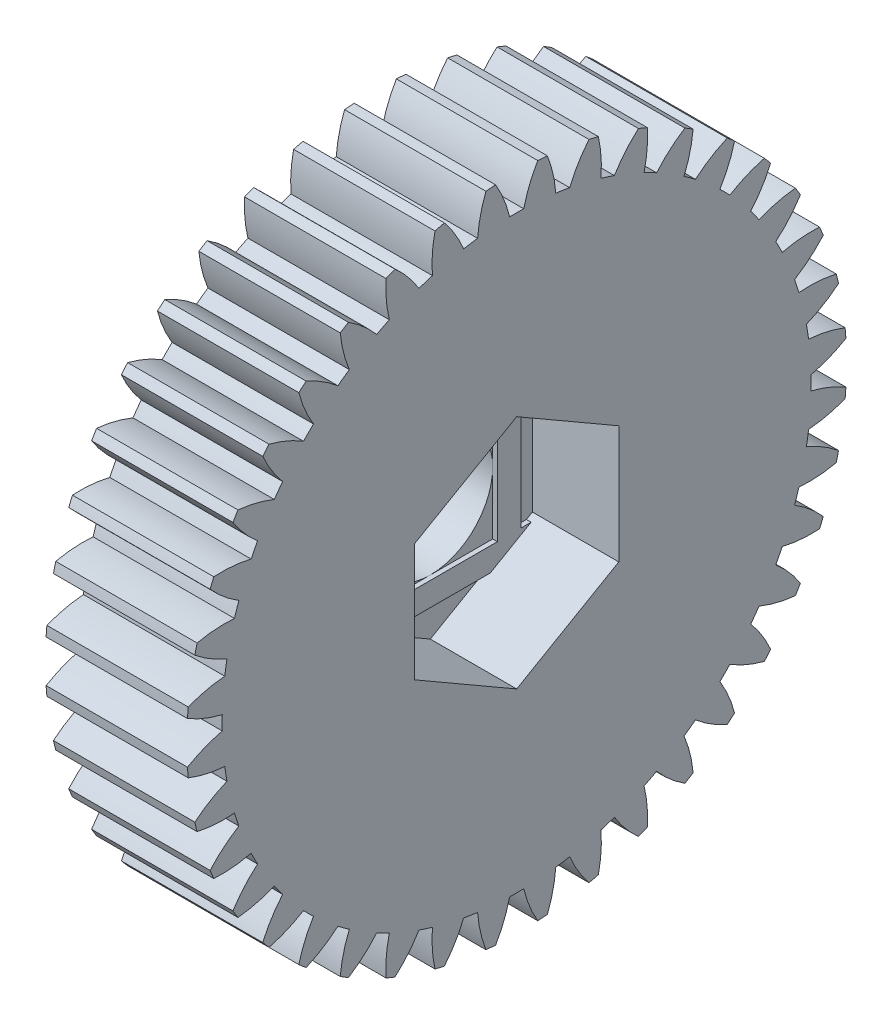
SolidWorks part; units mm, degrees
ref_plane "Plane1" through (0, 0, 0) normal (0, 0, 1) x (1, 0, 0)
ref_plane "Plane2" through (0, 0, 0) normal (0, 1, 0) x (1, 0, 0)
ref_plane "Plane3" through (0, 0, 0) normal (1, 0, 0) x (0, 0, -1)
sketch "HoldingSke" plane through (0, 0, 0) normal (0, 1, 0) x (1, 0, 0)
  line L0 (0, 0) -> (0.766, -0.6428)
  line L1 (-15, 0) -> (100, 0) construction
  line L2 (0, 0) -> (-2.1039, 2.3779)
  line L3 (0, 0) -> (-11.863, 4.5341)
  line L4 (0, 0) -> (6.6156, 5.5511)
  line L5 (0, 0) -> (-46.8476, -17.4728)
  line L6 (0, 0) -> (-7.4607, -5.0337)
  line L7 (-2.1039, 2.3779) -> (8.6586, 51.2059)
  line L8 (-76.2, 54.61) -> (-75.5, 54.61)
  line L9 (-71.009, 38.7566) -> (-53.1078, 45.2721)
  line L10 (-76.2, 71.12) -> (104.1128, 71.12)
  line L11 (0, 0) -> (-9, 0)
  line L12 (-76.2, 101.6) -> (-76.162, 101.6)
  line L13 (24.9733, 27.94) -> (52.9518, 28.4284)
  line L14 (24.9733, 27.94) -> (24.9743, 27.94)
  line L15 (24.9733, 27.94) -> (100.4006, 29.5858)
  line L16 (-63.627, -1) -> (-12.827, -1)
  circle A0 centre (0, 0) radius 2
  circle A1 centre (0, 0) radius 18.749
  circle A2 centre (0, 0) radius 37.5
  circle A3 centre (0, 0) radius 2
  dimension "MHD" = 37.498
  dimension "Hub_dia" = 75
  dimension "Bore" = 4
  dimension "MBD" = 4
  dimension "Num_teeth" = 40
  dimension "Pitch" = 1
  dimension "Overall_len" = 50
  dimension "Show_teeth" = 40
  dimension "Thickness" = 9
  dimension "OAL" = 50.0001
  dimension "T_dim" = 0.7
  dimension "Ap" = 20
  dimension "H" = 19.05
  dimension "Pitch_radius" = 180.3128
  dimension "Width" = 9
  dimension "Backlash" = 0.038
  dimension "Addendum_fac" = 1
  dimension "Dedendum_fac" = 1.25
  dimension "Clearance_fac" = 0.25
  dimension "Dedendum_add" = 0.001
  dimension "Module" = 1
sketch "BasProSke" plane through (0, 0, 0) normal (0, 1, 0) x (1, 0, 0)
  line L0 (-10, 0) -> (60, 0) construction
  line L1 (0, 0) -> (0, 21)
  line L2 (0, 0) -> (9, 0)
  line L3 (9, 0) -> (9, 21)
  line L4 (9, 21) -> (0, 21)
  dimension "Thickness" = 9
  dimension "Diameter" = 42
revolve "Base-Revolve" add sketch "BasProSke" angle 360 about L0
sketch "TooCutSke" plane through (0, 0, 0) normal (1, 0, 0) x (0, 0, -1)
  line L1 (0, 0) -> (0, 107) construction
  line L2 (0, 0) -> (-0.8517, 19.9819) construction
  line L3 (0, 0) -> (-3.1363, 39.8509) construction
  line L4 (-0.8517, 19.9819) -> (-1.5682, 19.9255) construction
  arc A0 (0.4487, 18.7436) -> (-0.4487, 18.7436) centre (0, 0) ccw
  arc A1 (1.3547, 20.9817) -> (-1.3547, 20.9817) centre (0, 0) ccw
  circle A2 centre (0, 0) radius 20 construction
  circle A3 centre (0, 0) radius 18.7939 construction
  arc A4 (-0.4487, 18.7436) -> (-1.3547, 20.9817) centre (-8.2322, 16.895) ccw
  arc A5 (1.3547, 20.9817) -> (0.4487, 18.7436) centre (8.2322, 16.895) ccw
  dimension "Root_dia" = 37.498
  dimension "Overcut_dia" = 42.0508
  dimension "Pitch_dia" = 40
  dimension "Base_dia" = 37.5877
  dimension "Flank_rad" = 8
  dimension "Half_ang" = 4.5
  dimension "Half_CT" = 0.7187
extrude "ToothCut" cut sketch "TooCutSke" along normal through all
fillet "Breaks" [suppressed] radius 0.02 tangent propagation no
fillet "RootFillets" [suppressed] radius 0.251
pattern_circular "TeethCuts" count 40 every 9 about axis through (-10, 0, 0) along (1, 0, 0) of "ToothCut", "RootFillets", "Breaks"
sketch "HubNeaOneSke" plane through (0, 0, 0) normal (-1, 0, 0) x (0, 0, 1)
  circle A0 centre (0, 0) radius 18.749
  dimension "Diameter" = 37.498
extrude "HubNearOne" [suppressed] add sketch "HubNeaOneSke" along normal blind 41.0001
sketch "HubNeaBotSke" plane through (0, 0, 0) normal (-1, 0, 0) x (0, 0, 1)
  circle A0 centre (0, 0) radius 18.749
  dimension "Diameter" = 37.498
extrude "HubNearBoth" [suppressed] add sketch "HubNeaBotSke" along normal blind 20.5
ref_plane "FarPln" through (9, 0, 0) normal (1, 0, 0) x (0, 0, -1)
sketch "HubFarSke" plane through (9, 0, 0) normal (1, 0, 0) x (0, 0, -1)
  circle A0 centre (0, 0) radius 18.749
  dimension "Diameter" = 37.498
extrude "HubFar" [suppressed] add sketch "HubFarSke" along normal blind 20.5
sketch "BorSke" plane through (0, 0, 0) normal (1, 0, 0) x (0, 0, -1)
  circle A0 centre (0, 0) radius 2
  dimension "Diameter" = 4
extrude "Bore" cut sketch "BorSke" along normal mid plane 100.0001
sketch "KeySke" plane through (0, 0, 0) normal (1, 0, 0) x (0, 0, -1)
  line L0 (-0.8, 0) -> (-0.8, 2.7)
  line L1 (-0.8, 2.7) -> (0.8, 2.7)
  line L2 (0.8, 2.7) -> (0.8, 0)
  line L3 (0, 0) -> (0, 34) construction
  line L4 (-0.8, 0) -> (0.8, 0)
  dimension "Offset" = 2.7
  dimension "Width" = 1.6
extrude "Keyway" [suppressed] cut sketch "KeySke" along normal mid plane 100.0001
pattern_circular "Keyway2" [suppressed] count 2 every 90 about axis through (-10, 0, 0) along (1, 0, 0) reverse direction yes
sketch "Sketch1" plane through (9, 0, 0) normal (1, 0, 0) x (0, 0, -1)
  line L1 (0, 7.5056) -> (-6.5, 3.7528)
  line L2 (-6.5, 3.7528) -> (-6.5, -3.7528)
  line L3 (-6.5, -3.7528) -> (0, -7.5056)
  line L4 (0, -7.5056) -> (6.5, -3.7528)
  line L5 (6.5, -3.7528) -> (6.5, 3.7528)
  line L6 (6.5, 3.7528) -> (0, 7.5056)
  circle A0 centre (0, 0) radius 7.5056
  circle A2 centre (0, 0) radius 6.5 construction
  circle A3 centre (0, 0) radius 3.9725
  dimension "D1" = 7.945
  dimension "D2" = 13
extrude "Cut-Extrude1" cut sketch "Sketch1" against normal blind 5.5 contours L1 L2 L3 L4 L5 L6
extrude "Cut-Extrude2" cut sketch "Sketch1<7>" against normal through all contours A3 region at (9, 0, 0)
sketch "Sketch1<7>" plane through (9, 0, 0) normal (1, 0, 0) x (0, 0, -1) same geometry as "Sketch1"
sketch "Sketch2" plane through (0, 0, 0) normal (-1, 0, 0) x (0, 0, 1)
  circle A0 centre (0, 0) radius 6
  circle A1 centre (0, 0) radius 4
  dimension "D1" = 12
  dimension "D2" = 8
extrude "Boss-Extrude1" add sketch "Sketch2" along normal blind 2.3
sketch "Sketch3" plane through (3.5, 0, 0) normal (1, 0, 0) x (0, 0, -1)
  line L1 (3.9725, 3.9725) -> (-3.9725, 3.9725)
  line L2 (3.9725, 3.9725) -> (3.9725, -3.9725)
  line L3 (3.9725, -3.9725) -> (-3.9725, -3.9725)
  line L4 (-3.9725, 3.9725) -> (-3.9725, -3.9725)
  line L6 (5.4725, 5.4725) -> (5.4725, -5.4725)
  line L7 (5.4725, -5.4725) -> (-5.4725, -5.4725)
  line L8 (-5.4725, 5.4725) -> (-5.4725, -5.4725)
  line L9 (5.4725, 5.4725) -> (-5.4725, 5.4725)
  line L10 (5.4725, 3.9725) -> (6.1194, 3.9725)
  line L11 (6.5, 3.7528) -> (0, 7.5056) construction
  line L12 (5.4725, -3.9725) -> (6.1194, -3.9725)
  line L13 (0, -7.5056) -> (6.5, -3.7528) construction
  line L14 (-5.4725, -3.9725) -> (-6.1194, -3.9725)
  line L15 (-6.5, -3.7528) -> (0, -7.5056) construction
  line L16 (-5.4725, 3.9725) -> (-6.1194, 3.9725)
  line L17 (0, 7.5056) -> (-6.5, 3.7528) construction
  circle A0 centre (0, 0) radius 3.9725 construction
  line M10 (6.5, 3.7528) -> (0, 7.5056)
  line M11 (0, 7.5056) -> (-6.5, 3.7528)
  line M13 (-6.5, -3.7528) -> (0, -7.5056)
  line M14 (0, -7.5056) -> (6.5, -3.7528)
  dimension "D1" = 1.5
extrude "Boss-Extrude2" add sketch "Sketch3" along normal blind 0.3 contours L9 L8 L7 L6 L4 L1 L2 L3 M10 M11 M13 M14 | L12 L6 M14 | L6 L10 M10 | L16 L8 M11 | L8 L14 M13 region at (3.5, 0, -5.3177) region at (3.5, 4.097, -5.6881) region at (3.5, -4.097, -5.6881) region at (3.5, 4.097, 5.6881) region at (3.5, -4.097, 5.6881)
equation "' \"Module@HoldingSke\" = 6.35"
equation "' \"Num_teeth@HoldingSke\" = 12"
equation "' \"Ap@HoldingSke\" =  20"
equation "' \"Ap@HoldingSke\" = 20"
equation "' \"Width@HoldingSke\" = 0.5 * 25.4"
equation "' \"Hub_dia@HoldingSke\"= 1 * 25.4"
equation "' \"Hub_dia@HoldingSke\" = 1 * 25.4"
equation "' \"Overall_len@HoldingSke\" = 1.0 * 25.4"
equation "' \"Bore@HoldingSke\" = 0.75 * 25.4"
equation "' \"T_dim@HoldingSke\" = 0.1 * 25.4"
equation "' \"Width@KeySke\" = 0.25 * 25.4"
equation "' \"Show_teeth@HoldingSke\" = 13"
equation "' \"Backlash@HoldingSke\" = 0.009 * 25.4"
equation "' \"Addendum_fac@HoldingSke\" = 1.0"
equation "' \"Dedendum_fac@HoldingSke\" = 1.25"
equation "' \"Dedendum_add@HoldingSke\" = 0.00005 * 25.4"
equation "' \"Clearance_fac@HoldingSke\" = 0.25"
equation "\"Pitch@HoldingSke\" = 1 / \"Module@HoldingSke\""
equation "\"Overcut_dia@TooCutSke\" = (\"Num_teeth@HoldingSke\" + 2 * \"Addendum_fac@HoldingSke\") / \"Pitch@HoldingSke\" + 0.002 * 25.4"
equation "\"Pitch_dia@TooCutSke\" = \"Num_teeth@HoldingSke\" / \"Pitch@HoldingSke\""
equation "\"Base_dia@TooCutSke\" = \"Num_teeth@HoldingSke\" / \"Pitch@HoldingSke\" * cos((\"Ap@HoldingSke\"  * 3.14159265 / 180))"
equation "\"Root_dia@TooCutSke\" = (\"Num_teeth@HoldingSke\" + 2) / \"Pitch@HoldingSke\" - 2 * (\"Addendum_fac@HoldingSke\" + \"Dedendum_fac@HoldingSke\") / \"Pitch@HoldingSke\" - \"Dedendum_add@HoldingSke\" * 2"
equation "\"Half_ang@TooCutSke\" = 180 / \"Num_teeth@HoldingSke\""
equation "\"Half_CT@TooCutSke\" = \"Num_teeth@HoldingSke\" / \"Pitch@HoldingSke\" * sin((3.14159265 / 2 / \"Num_teeth@HoldingSke\")) / 2 - 7 * \"Backlash@HoldingSke\" / 4"
equation "\"Flank_rad@TooCutSke\" = \"Num_teeth@HoldingSke\" / \"Pitch@HoldingSke\" / 5"
equation "\"Radius@RootFillets\" = \"Clearance_fac@HoldingSke\" / \"Pitch@HoldingSke\" + \"Dedendum_add@HoldingSke\""
equation "\"Break_rad@Breaks\" = 0.02 / \"Pitch@HoldingSke\""
equation "\"Thickness@HoldingSke\" = \"Width@HoldingSke\""
equation "\"OAL@HoldingSke\" = \"Thickness@HoldingSke\""
equation "\"MHD@HoldingSke\" = (\"Num_teeth@HoldingSke\" + 2) / \"Pitch@HoldingSke\" - 2 * (\"Addendum_fac@HoldingSke\" + \"Dedendum_fac@HoldingSke\")  / \"Pitch@HoldingSke\" - \"Dedendum_add@HoldingSke\" * 2"
equation "\"MBD@HoldingSke\" = (\"Num_teeth@HoldingSke\" + 2) / \"Pitch@HoldingSke\" - 2 * (\"Addendum_fac@HoldingSke\" + \"Dedendum_fac@HoldingSke\")  / \"Pitch@HoldingSke\" - \"Dedendum_add@HoldingSke\" * 2 - 0.002 * 25.4"
equation "\"MHD@HoldingSke\" = ((sgn( \"MHD@HoldingSke\" - \"Hub_dia@HoldingSke\" )-1)*( \"MHD@HoldingSke\" - \"Hub_dia@HoldingSke\" ))/-2+ \"Hub_dia@HoldingSke\""
equation "\"MBD@HoldingSke\" = ((sgn( \"MBD@HoldingSke\" - \"Bore@HoldingSke\" )-1)*( \"MBD@HoldingSke\" - \"Bore@HoldingSke\" ))/-2+ \"Bore@HoldingSke\""
equation "\"OAL@HoldingSke\" = ((sgn( \"OAL@HoldingSke\" - \"Overall_len@HoldingSke\" )+1)*( \"OAL@HoldingSke\" - \"Overall_len@HoldingSke\" ))/2 + \"Overall_len@HoldingSke\" + 0.000002 * 25.4"
equation "\"Num_teeth@TeethCuts\" = int( \"Show_teeth@HoldingSke\" ) + 1"
equation "\"Num_teeth@TeethCuts\" = ((sgn( \"Num_teeth@TeethCuts\" - \"Num_teeth@HoldingSke\" )-1)*( \"Num_teeth@TeethCuts\" - \"Num_teeth@HoldingSke\" ))/-2+ \"Num_teeth@HoldingSke\""
equation "\"Num_teeth@TeethCuts\" = ((sgn( \"Num_teeth@TeethCuts\" - 2.0)+1)*( \"Num_teeth@TeethCuts\" - 2.0))/2 +2.0"
equation "\"Angle@TeethCuts\" = 360.0 / \"Num_teeth@HoldingSke\""
equation "\"Diameter@BasProSke\" = (\"Num_teeth@HoldingSke\" + 2 * \"Addendum_fac@HoldingSke\") / \"Pitch@HoldingSke\""
equation "\"Thickness@BasProSke\"  = \"Thickness@HoldingSke\""
equation "' \"Fillet_rad@BasProSke\" =  \"Thickness@HoldingSke\" * 0.05"
equation "' \"Fillet_rad@BasProSke\" = \"Thickness@HoldingSke\" * 0.05"
equation "\"MHD@HoldingSke\" = ((sgn( \"MHD@HoldingSke\" - \"Root_dia@TooCutSke\" )-1)*( \"MHD@HoldingSke\" - \"Root_dia@TooCutSke\" ))/-2+ \"Root_dia@TooCutSke\""
equation "\"Diameter@HubNeaOneSke\" = \"MHD@HoldingSke\""
equation "\"Length@HubNearOne\" = \"OAL@HoldingSke\" - \"Thickness@BasProSke\""
equation "\"Diameter@HubNeaBotSke\" = \"MHD@HoldingSke\""
equation "\"Length@HubNearBoth\" = ( \"OAL@HoldingSke\" - \"Thickness@BasProSke\" ) / 2.0"
equation "\"Thickness@FarPln\" = \"Thickness@BasProSke\""
equation "\"Diameter@HubFarSke\" = \"MHD@HoldingSke\""
equation "\"Length@HubFar\" = ( \"OAL@HoldingSke\" - \"Thickness@BasProSke\" ) / 2.0"
equation "\"Diameter@BorSke\" = \"MBD@HoldingSke\""
equation "\"D1@Bore\" = \"OAL@HoldingSke\" * 2.0"
equation "\"D1@Keyway\" = \"OAL@HoldingSke\" * 2.0"
equation "\"Offset@KeySke\" = \"T_dim@HoldingSke\" + \"MBD@HoldingSke\" / 2.0"
